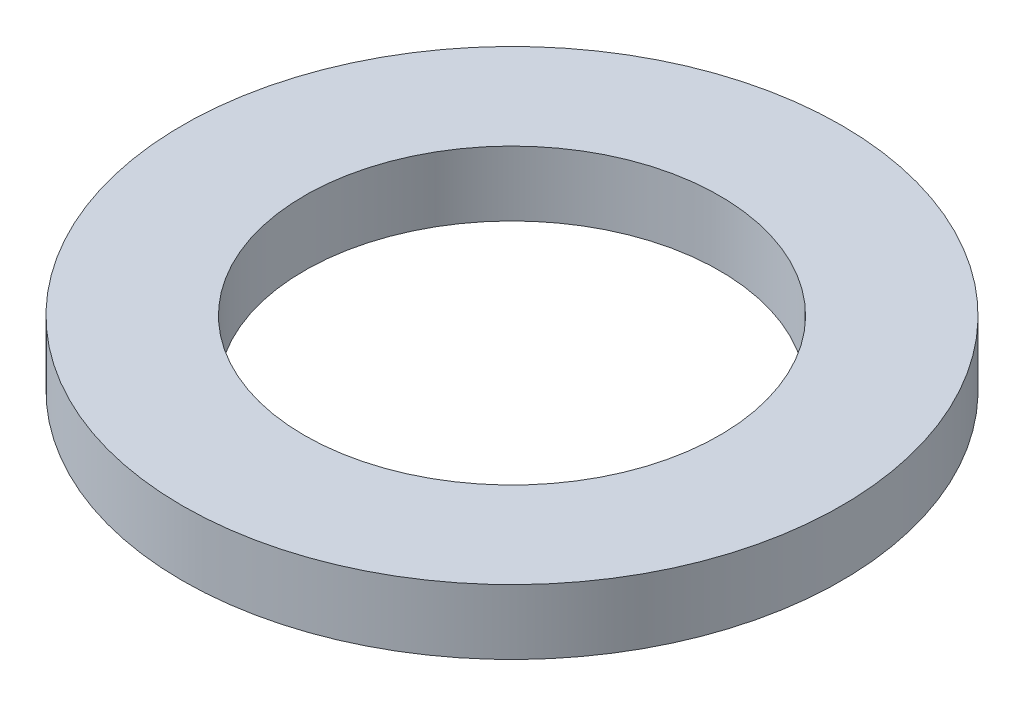
SolidWorks part; units mm, degrees
ref_plane "Front Plane" through (0, 0, 0) normal (0, 0, 1) x (1, 0, 0)
ref_plane "Top Plane" through (0, 0, 0) normal (0, 1, 0) x (1, 0, 0)
ref_plane "Right Plane" through (0, 0, 0) normal (1, 0, 0) x (0, 0, -1)
sketch "Sketch1" plane through (0, 0, 0) normal (0, 1, 0) x (1, 0, 0)
  circle A0 centre (0, 0) radius 25.4
extrude "Boss-Extrude1" add sketch "Sketch1" along normal blind 5
sketch "Sketch2" plane through (0, 5, 0) normal (0, 1, 0) x (1, 0, 0)
  circle A0 centre (0, 0) radius 16
extrude "Cut-Extrude1" cut sketch "Sketch2" against normal blind 5
